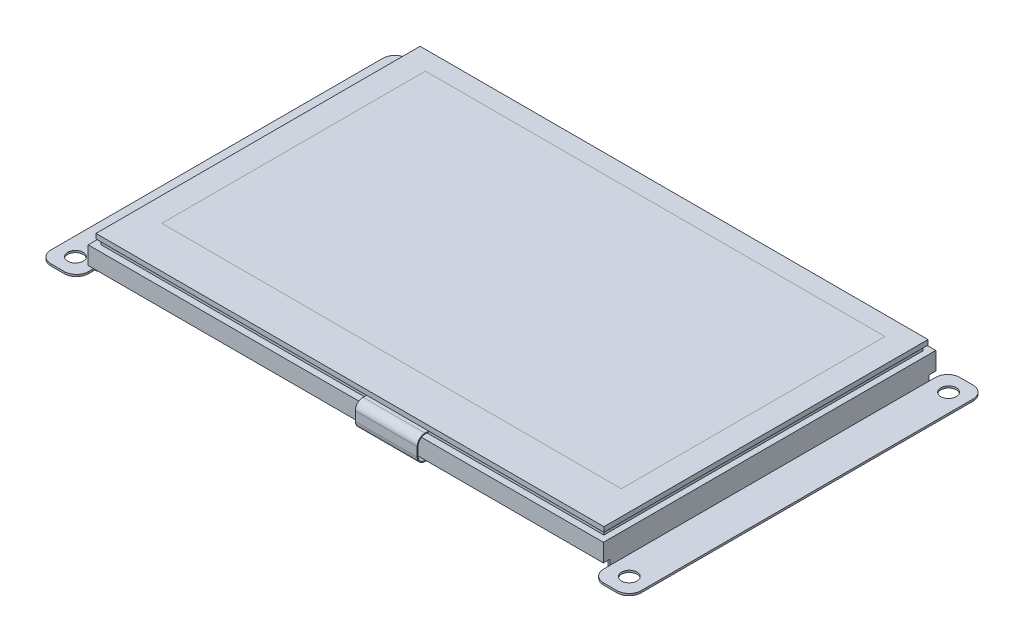
SolidWorks part; units mm, degrees
ref_plane "前基準面" through (0, 0, 0) normal (0, 0, 1) x (1, 0, 0)
ref_plane "上基準面" through (0, 0, 0) normal (0, 1, 0) x (1, 0, 0)
ref_plane "右基準面" through (0, 0, 0) normal (1, 0, 0) x (0, 0, -1)
sketch "草圖1" plane through (0, 0, 0) normal (0, 1, 0) x (1, 0, 0)
  line L1 (-52.5, -33.5) -> (52.5, -33.5)
  line L2 (-52.5, -33.5) -> (-52.5, 33.5)
  line L3 (-52.5, 33.5) -> (52.5, 33.5)
  line L4 (52.5, -33.5) -> (52.5, 33.5)
  line L5 (-52.5, -33.5) -> (52.5, 33.5) construction
  line L6 (-52.5, 33.5) -> (52.5, -33.5) construction
  point P0 (0, 0)
  dimension "D1" = 105
  dimension "D2" = 67
extrude "填料-伸長1" add sketch "草圖1" against normal blind 1
sketch "草圖2" plane through (0, -1, 0) normal (0, -1, 0) x (1, 0, 0)
  line L16 (52, -33) -> (52, 33)
  line L17 (-52, -33) -> (52, -33)
  line L18 (-52, 33) -> (-52, -33)
  line L19 (52, 33) -> (-52, 33)
  line L20 (52, -33) -> (52, 33)
  line L21 (-52, -33) -> (52, -33)
  line L22 (-52, 33) -> (-52, -33)
  line L23 (52, 33) -> (-52, 33)
  dimension "D1" = 0.5
extrude "填料-伸長2" add sketch "草圖2" along normal blind 1
sketch "草圖3" plane through (0, -2, 0) normal (0, -1, 0) x (1, 0, 0)
  line L1 (-53.25, -34.35) -> (53.25, -34.35)
  line L2 (-53.25, -34.35) -> (-53.25, 34.35)
  line L3 (-53.25, 34.35) -> (53.25, 34.35)
  line L4 (53.25, -34.35) -> (53.25, 34.35)
  line L5 (-53.25, -34.35) -> (53.25, 34.35) construction
  line L6 (-53.25, 34.35) -> (53.25, -34.35) construction
  point P0 (0, 0)
  dimension "D1" = 68.7
  dimension "D2" = 106.5
extrude "填料-伸長3" add sketch "草圖3" along normal blind 3.7
sketch "草圖4" plane through (0, -5.7, 0) normal (0, -1, 0) x (1, 0, 0)
  line L0 (-53.25, 34.35) -> (-53.25, -34.35) construction
  line L1 (-53.25, 33) -> (-52.85, 33)
  line L2 (-53.25, 33) -> (-53.25, -33)
  line L3 (-53.25, -33) -> (-52.85, -33)
  line L4 (-52.85, 33) -> (-52.85, -33)
  line L5 (0, 40.4508) -> (0, -43.212) construction
  line L6 (52.85, 33) -> (52.85, -33)
  line L7 (53.25, -33) -> (52.85, -33)
  line L8 (53.25, 33) -> (53.25, -33)
  line L9 (53.25, 33) -> (52.85, 33)
  point P6 (-53.25, 0)
  dimension "D1" = 0.4
  dimension "D2" = 66
extrude "填料-伸長4" add sketch "草圖4" along normal blind 1.5
sketch "草圖5" plane through (0, -7.2, 0) normal (0, -1, 0) x (1, 0, 0)
  line L0 (0, 40.4599) -> (0, -40.6534) construction
  line L1 (-53.25, 33) -> (-53.25, -33) construction
  line L2 (-55.75, 36.8) -> (-58.5, 36.8)
  line L3 (-53.25, 34.3) -> (-53.25, -34.3)
  line L4 (-55.75, -36.8) -> (-58.5, -36.8)
  line L5 (-61, 34.3) -> (-61, -34.3)
  line L6 (0, 0) -> (-72.828, 0) construction
  line L7 (61, 34.3) -> (61, -34.3)
  line L8 (55.75, -36.8) -> (58.5, -36.8)
  line L9 (53.25, 34.3) -> (53.25, -34.3)
  line L10 (55.75, 36.8) -> (58.5, 36.8)
  arc A0 (-61, -34.3) -> (-58.5, -36.8) centre (-58.5, -34.3) ccw
  arc A1 (-53.25, -34.3) -> (-55.75, -36.8) centre (-55.75, -34.3) cw
  arc A2 (-53.25, 34.3) -> (-55.75, 36.8) centre (-55.75, 34.3) ccw
  arc A3 (-58.5, 36.8) -> (-61, 34.3) centre (-58.5, 34.3) ccw
  circle A4 centre (-57.25, 33) radius 1.6
  circle A5 centre (-57.25, -33) radius 1.6
  circle A6 centre (57.25, -33) radius 1.6
  circle A7 centre (57.25, 33) radius 1.6
  arc A8 (58.5, 36.8) -> (61, 34.3) centre (58.5, 34.3) cw
  arc A9 (53.25, 34.3) -> (55.75, 36.8) centre (55.75, 34.3) cw
  arc A10 (53.25, -34.3) -> (55.75, -36.8) centre (55.75, -34.3) ccw
  arc A11 (61, -34.3) -> (58.5, -36.8) centre (58.5, -34.3) cw
  point P10 (-53.25, 0)
  point P13 (-61, -36.8)
  point P18 (-53.25, 36.8)
  point P21 (-61, 36.8)
  point P43 (61, 36.8)
  point P44 (53.25, 36.8)
  point P45 (61, -36.8)
  dimension "D3" = 2.5
  dimension "D6" = 3.2
  dimension "D1" = 73.6
  dimension "D2" = 122
  dimension "D4" = 66
  dimension "D5" = 114.5
extrude "填料-伸長5" add sketch "草圖5" against normal blind 0.4
sketch "草圖6" plane through (0, 0, 0) normal (0, 1, 0) x (1, 0, 0)
  line L0 (-52.5, -33.5) -> (52.5, -33.5) construction
  line L1 (-47.5, 29.6) -> (47.5, 29.6)
  line L2 (-47.5, 29.6) -> (-47.5, -24.9)
  line L3 (-47.5, -24.9) -> (47.5, -24.9)
  line L4 (47.5, 29.6) -> (47.5, -24.9)
  point P4 (0, 29.6)
  dimension "D1" = 95
  dimension "D2" = 54.5
  dimension "D3" = 8.6
split line "分割線1"
sketch "草圖7" plane through (0, -5.7, 0) normal (0, -1, 0) x (1, 0, 0)
  line L0 (-53.25, -34.35) -> (53.25, -34.35) construction
  line L1 (-26.35, -29.35) -> (18.65, -29.35)
  line L2 (-26.35, -29.35) -> (-26.35, 8.65)
  line L3 (-26.35, 8.65) -> (18.65, 8.65)
  line L4 (18.65, -29.35) -> (18.65, 8.65)
  line L5 (-52.85, -33) -> (-52.85, 33) construction
  dimension "D1" = 38
  dimension "D2" = 45
  dimension "D3" = 5
  dimension "D4" = 26.5
extrude "填料-伸長6" add sketch "草圖7" along normal blind 1.2
sketch "草圖8" plane through (0, -6.9, 0) normal (0, -1, 0) x (1, 0, 0)
  line L0 (-26.35, 8.65) -> (-26.35, -29.35) construction
  line L1 (-26.35, -28.35) -> (-18.65, -28.35)
  line L2 (-26.35, -28.35) -> (-26.35, -13.35)
  line L3 (-26.35, -13.35) -> (-18.65, -13.35)
  line L4 (-18.65, -28.35) -> (-18.65, -13.35)
  line L5 (-26.35, -29.35) -> (18.65, -29.35) construction
  line L6 (-25.85, 7.65) -> (-17.35, 7.65)
  line L7 (-25.85, 7.65) -> (-25.85, -0.85)
  line L8 (-25.85, -0.85) -> (-17.35, -0.85)
  line L9 (-17.35, 7.65) -> (-17.35, -0.85)
  line L10 (6.65, -12.95) -> (21.65, -12.95)
  line L11 (6.65, -12.95) -> (6.65, -28.15)
  line L12 (6.65, -28.15) -> (21.65, -28.15)
  line L13 (21.65, -12.95) -> (21.65, -28.15)
  line L14 (-11.05, 8.15) -> (9.95, 8.15)
  line L15 (-11.05, 8.15) -> (-11.05, 3.65)
  line L16 (-11.05, 3.65) -> (9.95, 3.65)
  line L17 (9.95, 8.15) -> (9.95, 3.65)
  line L18 (18.65, 8.65) -> (-26.35, 8.65) construction
  line L20 (18.65, -29.35) -> (18.65, 8.65) construction
  line M15 (-26.35, 8.65) -> (-26.35, -29.35)
  line M17 (18.65, -29.35) -> (18.65, 8.65)
  dimension "D1" = 15
  dimension "D2" = 7.7
  dimension "D3" = 8.5
  dimension "D4" = 8.5
  dimension "D5" = 4.5
  dimension "D6" = 21
  dimension "D7" = 15
  dimension "D8" = 15.2
  dimension "D9" = 1.2
  dimension "D10" = 0.5
  dimension "D11" = 0.5
  dimension "D12" = 1
  dimension "D13" = 1
  dimension "D14" = 3
  dimension "D15" = 8.7
extrude "填料-伸長7" add sketch "草圖8" along normal blind 5.8 contours L1 L4 L3 M15 region at (-22.5, -6.9, -20.85)
extrude "填料-伸長8" add sketch "草圖8<3>" along normal blind 3 contours L9 L6 L7 L8 region at (-21.6, -6.9, 3.4)
sketch "草圖8<3>" plane through (0, -6.9, 0) normal (0, -1, 0) x (1, 0, 0) same geometry as "草圖8"
extrude "填料-伸長9" add sketch "草圖8<4>" along normal blind 2 contours L17 L14 L15 L16 region at (-0.55, -6.9, 5.9)
sketch "草圖8<4>" plane through (0, -6.9, 0) normal (0, -1, 0) x (1, 0, 0) same geometry as "草圖8"
extrude "填料-伸長10" add sketch "草圖8<5>" along normal blind 2 contours L11 L12 L10 M17 | L13 L10 L12 M17 region at (12.65, -6.9, -20.55) region at (20.15, -6.9, -20.55)
sketch "草圖8<5>" plane through (0, -6.9, 0) normal (0, -1, 0) x (1, 0, 0) same geometry as "草圖8"
sketch "草圖9" plane through (53.25, 0, 0) normal (1, 0, 0) x (0, 0, -1)
  line L0 (-34.35, -5.7) -> (-34.35, -2) construction
  line L1 (-35.35, -3) -> (-35.35, -4.9) construction
  line L2 (-33.85, -6.4) -> (-29.85, -6.4) construction
  line L3 (-33.85, -1.5) -> (-33, -1.5) construction
  line L4 (-33, -2) -> (-33, -1) construction
  line L5 (-33, -5.7) -> (-34.35, -5.7) construction
  line L6 (-33.85, -6.3) -> (-29.85, -6.3)
  line L7 (-35.25, -3) -> (-35.25, -4.9)
  line L8 (-33.85, -1.6) -> (-33, -1.6)
  line L9 (-33.85, -6.5) -> (-29.85, -6.5)
  line L10 (-35.45, -3) -> (-35.45, -4.9)
  line L11 (-33.85, -1.4) -> (-33, -1.4)
  line L12 (-33, -1.4) -> (-33, -1.6)
  line L13 (-29.85, -6.3) -> (-29.85, -6.5)
  arc A0 (-35.35, -3) -> (-33.85, -1.5) centre (-33.85, -3) cw construction
  arc A1 (-35.35, -4.9) -> (-33.85, -6.4) centre (-33.85, -4.9) ccw construction
  arc A2 (-35.25, -4.9) -> (-33.85, -6.3) centre (-33.85, -4.9) ccw
  arc A3 (-35.25, -3) -> (-33.85, -1.6) centre (-33.85, -3) cw
  arc A4 (-35.45, -4.9) -> (-33.85, -6.5) centre (-33.85, -4.9) ccw
  arc A5 (-35.45, -3) -> (-33.85, -1.4) centre (-33.85, -3) cw
  dimension "D1" = 1
  dimension "D2" = 1.5
  dimension "D3" = 0.7
  dimension "D4" = 4
  dimension "D5" = 0.1
  dimension "D6" = 0.1
extrude "填料-伸長11" add sketch "草圖9" against normal blind 12.8 from offset 37.4 offset against normal yes
